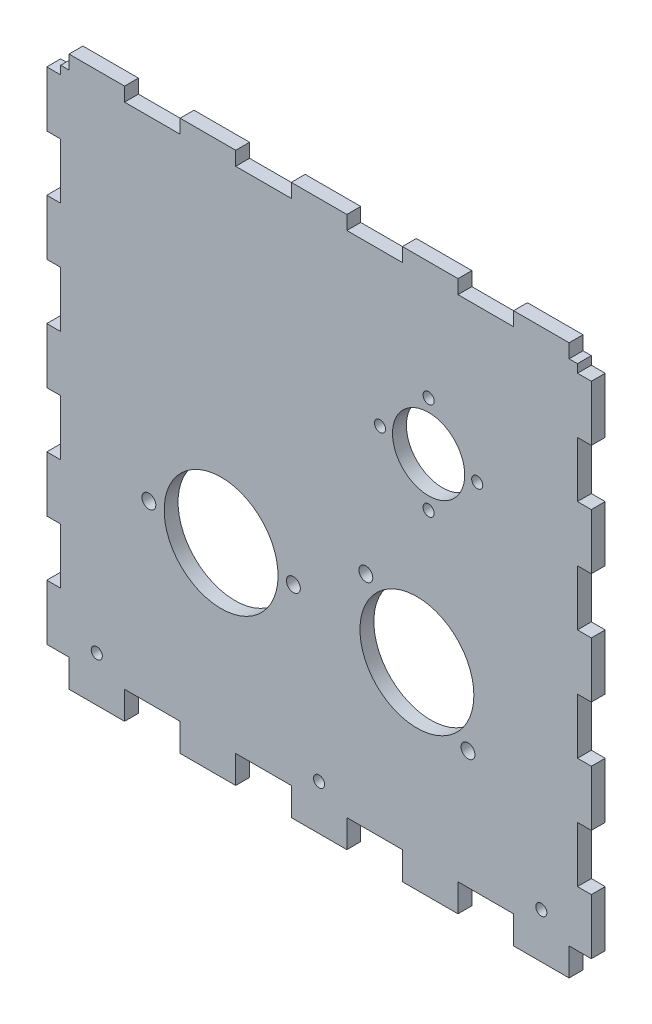
SolidWorks part; units mm, degrees
ref_plane "정면" through (0, 0, 0) normal (0, 0, 1) x (1, 0, 0)
ref_plane "윗면" through (0, 0, 0) normal (0, 1, 0) x (1, 0, 0)
ref_plane "우측면" through (0, 0, 0) normal (1, 0, 0) x (0, 0, -1)
sketch "스케치1" plane through (0, 0, 0) normal (0, 0, 1) x (1, 0, 0)
  line L0 (-35.25, 48.411) -> (-35.25, -111.4061) construction
  line L1 (-93, 91.5) -> (93, 91.5)
  line L2 (-93, 91.5) -> (-93, -91.5)
  line L3 (-93, -91.5) -> (93, -91.5)
  line L4 (93, 91.5) -> (93, -91.5)
  line L5 (-93, 91.5) -> (93, -91.5) construction
  line L6 (-93, -91.5) -> (93, 91.5) construction
  line L7 (39.4226, 64.8355) -> (39.4226, -71.9738) construction
  line L8 (0, 68.0997) -> (0, -64.9282) construction
  line L9 (67.9316, -30.5) -> (15.9316, -30.5) construction
  line L10 (11.3218, -6.6001) -> (50.8051, -46.0834) construction
  circle A1 centre (-35.25, -28.5) radius 20.5
  circle A4 centre (-61.25, -28.5) radius 2.5
  circle A5 centre (-9.25, -28.5) radius 2.5
  circle A6 centre (39.4226, 36.5) radius 21 construction
  circle A9 centre (35.2216, -30.5) radius 20.5
  circle A10 centre (16.8368, -12.1152) radius 2.5
  circle A11 centre (53.6064, -48.8848) radius 2.5
  circle A12 centre (39.4226, 36.5) radius 17.5 construction
  circle A13 centre (39.4226, 19) radius 2
  circle A14 centre (39.4226, 36.5) radius 13
  circle A18 centre (21.9226, 36.5) radius 2
  circle A19 centre (39.4226, 54) radius 2
  circle A20 centre (56.9226, 36.5) radius 2
  point P0 (0, 0)
  point P44 (39.4226, 36.5)
  dimension "D3" = 41
  dimension "D8" = 52
  dimension "D9" = 5
  dimension "D10" = 55
  dimension "D11" = 42
  dimension "D12" = 4
  dimension "D14" = 41
  dimension "D15" = 70.5
  dimension "D17" = 5
  dimension "D20" = 26
  dimension "D1" = 183
  dimension "D2" = 186
  dimension "D4" = 3.5
  dimension "D5" = 63
  dimension "D6" = 99
  dimension "D7" = 35.25
  dimension "D13" = 61
  dimension "D16" = 45
  dimension "D18" = 26
  dimension "D19" = 26
  dimension "D21" = 4
extrude "보스-돌출1" add sketch "스케치1" along normal blind 5
sketch "스케치2" plane through (0, 0, 5) normal (0, 0, 1) x (1, 0, 0)
  line L1 (-93, -91.5) -> (-98, -91.5)
  line L2 (-93, -91.5) -> (-93, -71.5)
  line L3 (-93, -71.5) -> (-98, -71.5)
  line L4 (-98, -91.5) -> (-98, -71.5)
  dimension "D1" = 5
  dimension "D2" = 20
extrude "보스-돌출2" add sketch "스케치2" against normal up to surface (5 mm away) up to face at (0, 0, 0)
pattern_linear "선형 패턴1" count 5 spacing 40 along (0, 1, 0) of "보스-돌출2"
mirror "대칭 복사1" about plane through (0, 0, 0) normal (1, 0, 0) of "선형 패턴1"
sketch "스케치3" plane through (0, 0, 5) normal (0, 0, 1) x (1, 0, 0)
  line L0 (93, 91.5) -> (-93, 91.5) construction
  line L1 (10, 91.5) -> (-10, 91.5)
  line L2 (10, 91.5) -> (10, 96.5)
  line L3 (10, 96.5) -> (-10, 96.5)
  line L4 (-10, 91.5) -> (-10, 96.5)
  line L5 (0, 262.1917) -> (0, -69.1917) construction
  point P9 (0, 96.5)
  dimension "D1" = 20
  dimension "D2" = 5
extrude "보스-돌출3" add sketch "스케치3" against normal up to surface (5 mm away) up to face at (0, 7.65, 0)
pattern_linear "선형 패턴2" count 3 spacing 40 along (1, 0, 0) of "보스-돌출3"
pattern_linear "선형 패턴3" count 3 spacing 40 along (-1, 0, 0) of "보스-돌출3"
sketch "스케치4" plane through (0, 0, 5) normal (0, 0, 1) x (1, 0, 0)
  line L0 (-98, -91.5) -> (98, -91.5) construction
  line L1 (-10, -91.5) -> (10, -91.5)
  line L2 (-10, -91.5) -> (-10, -101.5)
  line L3 (-10, -101.5) -> (10, -101.5)
  line L4 (10, -91.5) -> (10, -101.5)
  line L5 (0, -83.6889) -> (0, -110.8852) construction
  dimension "D1" = 20
  dimension "D2" = 10
extrude "보스-돌출4" add sketch "스케치4" against normal up to surface (5 mm away) up to face at (0, 36.4333, 0)
pattern_linear "선형 패턴4" count 3 spacing 40 along (1, 0, 0) of "보스-돌출4"
pattern_linear "선형 패턴5" count 3 spacing 40 along (-1, 0, 0) of "선형 패턴4"
sketch "스케치5" plane through (0, 0, 0) normal (0, 0, -1) x (-1, 0, 0)
  line L0 (0, -66.2628) -> (0, -108.7434) construction
  line L1 (-10, -91.5) -> (-30, -91.5) construction
  circle A0 centre (0, -85.2) radius 2
  point P5 (0, -66.2628)
  dimension "D1" = 4
  dimension "D2" = 6.3
extrude "컷-돌출1" cut sketch "스케치5" against normal up to next
pattern_linear "선형 패턴6" count 2 spacing 80 along (1, 0, 0) of "컷-돌출1"
pattern_linear "선형 패턴7" count 2 spacing 80 along (-1, 0, 0) of "컷-돌출1"
